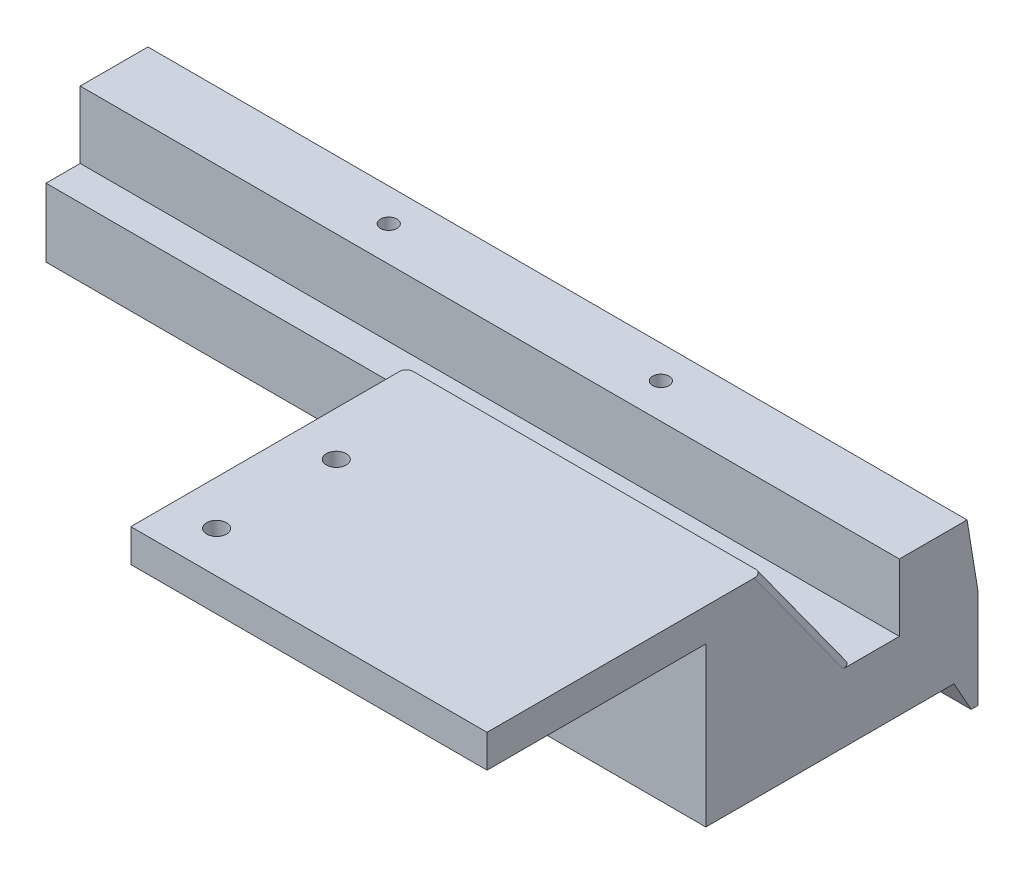
SolidWorks part; units mm, degrees
ref_plane "Płaszczyzna przednia" through (0, 0, 0) normal (0, 0, 1) x (1, 0, 0)
ref_plane "Płaszczyzna górna" through (0, 0, 0) normal (0, 1, 0) x (1, 0, 0)
ref_plane "Płaszczyzna prawa" through (0, 0, 0) normal (1, 0, 0) x (0, 0, -1)
sketch "Szkic1" plane through (0, 0, 0) normal (0, 0, 1) x (1, 0, 0)
  line L1 (-58.3066, 32.0248) -> (61.4934, 32.0248)
  line L2 (-58.3066, 32.0248) -> (-58.3066, 22.0248)
  line L3 (-58.3066, 22.0248) -> (61.4934, 22.0248)
  line L4 (61.4934, 32.0248) -> (61.4934, 22.0248)
  dimension "D1" = 119.8
  dimension "D2" = 10
extrude "Dodanie-wyciągnięcie2" add sketch "Szkic1" along normal blind 38.3 contours L2 L3 L4 L1
sketch "Szkic21" plane through (0, 32.0248, 0) normal (0, 1, 0) x (1, 0, 0)
  line L0 (61.4934, -38.3) -> (61.4934, 0) construction
  line L1 (-58.3066, 0) -> (61.4934, 0)
  line L2 (-58.3066, 0) -> (-58.3066, -10)
  line L3 (-58.3066, -10) -> (61.4934, -10)
  line L4 (61.4934, 0) -> (61.4934, -10)
extrude "Dodanie-wyciągnięcie3" add sketch "Szkic21" along normal blind 9.8
sketch "Szkic22" plane through (0, 22.0248, 0) normal (0, -1, 0) x (1, 0, 0)
  line L0 (-58.3066, 4.88) -> (-18.3066, 4.88) construction
  line L1 (-58.3066, 38.3) -> (-58.3066, 0) construction
  line L2 (-18.3066, 4.88) -> (21.4934, 4.88) construction
  line L3 (21.4934, 4.88) -> (61.4934, 4.88) construction
  line L4 (61.4934, 38.3) -> (61.4934, 0) construction
  line L5 (1.9729, 4.88) -> (1.9729, 0) construction
  line L6 (-58.3066, 0) -> (61.4934, 0) construction
hole_wizard "Pogłębienie walcowe pod M2 wkręt do części metalowych z łbem stożkowym ściętym2" positions "Szkic23" profile "Szkic24" counterbore size "M2" standard "Ansi Metric" end condition through all
sketch "Szkic23" plane through (0, 22.0248, 0) normal (0, -1, 0) x (-1, 0, 0)
  point P0 (-21.4934, -4.88)
  point P3 (18.3066, -4.88)
sketch "Szkic24" plane through (21.4934, 22.0248, 4.88) normal (1, 0, 0) x (0, 0, -1)
  line L0 (0, 0) -> (0, 19.8)
  line L1 (0, 19.8) -> (1.2, 19.8)
  line L3 (1.2, 19.8) -> (1.2, 1.6)
  line L4 (1.2, 1.6) -> (2.5, 1.6)
  line L5 (2.5, 1.6) -> (2.5, 0)
  line L7 (2.5, 0) -> (0, 0)
  line L11 (0, -6.35) -> (0, 107.95) construction
  dimension "Średnica otworu na wylot" = 2.4
  dimension "Głębokość otworu na wylot" = 19.8
  dimension "Średnica pogłębienia walcowego" = 5
  dimension "Głębokość pogłębienia walcowego" = 1.6
sketch "Szkic28" plane through (0, 22.0248, 0) normal (0, -1, 0) x (1, 0, 0)
  line L0 (36.4934, 0) -> (36.4934, 23.3) construction
  line L1 (-58.3066, 0) -> (61.4934, 0) construction
  line L2 (36.4934, 23.3) -> (61.4934, 23.3) construction
  line L3 (61.4934, 38.3) -> (61.4934, 0) construction
  line L4 (-58.3066, 38.3) -> (61.4934, 38.3) construction
  circle A0 centre (36.4934, 23.3) radius 11.1
  dimension "D1" = 15
extrude "Wytnij-wyciągnięcie1" cut sketch "Szkic28" against normal blind 7.2
sketch "Szkic31" plane through (61.4934, 0, 0) normal (1, 0, 0) x (0, 0, -1)
  line L0 (-10, 32.0248) -> (-10, 71.9248)
  line L2 (0, 41.2325) -> (0, 32.0248)
  line L6 (0, 41.8248) -> (0, 22.0248) construction
  line L8 (0, 32.0248) -> (1.5, 32.0248)
  line L10 (-10, 32.0248) -> (1.5, 32.0248)
  line L12 (-10, 71.9248) -> (-5, 71.9248)
  line L13 (-5, 71.9248) -> (1.5, 32.0248)
  line L14 (-0.4105, 43.7521) -> (0.2752, 39.543)
  line L15 (0.2752, 39.543) -> (3.3905, 40.0505)
  line L16 (3.3905, 40.0505) -> (-0.4105, 43.7521)
  line M5 (0, 22.0248) -> (0, 41.8248)
  line M6 (0, 41.8248) -> (-10, 41.8248)
extrude "Wytnij-wyciągnięcie4" cut sketch "Szkic31" against normal blind 124.8 contours L13 M6 M5 region at (61.4934, 41.6274, 0.0322)
extrude "Dodanie-wyciągnięcie5" add sketch "Szkic31<5>" against normal blind 119.8 contours L13 L8 M5 region at (61.4934, 35.0941, -0.5)
sketch "Szkic31<5>" plane through (61.4934, 0, 0) normal (1, 0, 0) x (0, 0, -1) same geometry as "Szkic31"
sketch "Szkic34" plane through (0, 0, 0) normal (0, 0, -1) x (-1, 0, 0)
  line L1 (-61.4934, 32.0248) -> (58.3066, 32.0248)
  line L2 (-61.4934, 32.0248) -> (-61.4934, 22.0248)
  line L3 (-61.4934, 22.0248) -> (58.3066, 22.0248)
  line L4 (58.3066, 32.0248) -> (58.3066, 22.0248)
extrude "Dodanie-wyciągnięcie6" add sketch "Szkic34" along normal blind 1.5
sketch "Szkic37" plane through (0, 32.0248, 0) normal (0, 1, 0) x (1, 0, 0)
  line L1 (61.4934, -38.3) -> (9.3934, -38.3)
  line L2 (61.4934, -38.3) -> (61.4934, -30)
  line L3 (61.4934, -30) -> (9.3934, -30)
  line L4 (9.3934, -38.3) -> (9.3934, -30)
extrude "Dodanie-wyciągnięcie8" add sketch "Szkic37" along normal blind 18
sketch "Szkic38" plane through (0, 0, 38.3) normal (0, 0, 1) x (1, 0, 0)
  line L0 (61.4934, 50.0248) -> (61.4934, 22.0248) construction
  line L1 (9.3934, 50.0248) -> (61.4934, 50.0248)
  line L2 (9.3934, 50.0248) -> (9.3934, 45.2248)
  line L3 (9.3934, 45.2248) -> (61.4934, 45.2248)
  line L4 (61.4934, 50.0248) -> (61.4934, 45.2248)
extrude "Dodanie-wyciągnięcie11" add sketch "Szkic38" along normal blind 32
sketch "Szkic40" plane through (0, 45.2248, 0) normal (0, -1, 0) x (1, 0, 0)
  line L0 (9.3934, 44.15) -> (61.4934, 44.15) construction
  line L1 (9.3934, 70.3) -> (9.3934, 38.3) construction
  line L2 (61.4934, 70.3) -> (61.4934, 38.3) construction
  line L3 (9.3934, 38.3) -> (61.4934, 38.3) construction
  line L4 (49.3934, 44.15) -> (49.3934, 38.3) construction
  line L5 (9.3934, 66.65) -> (61.4934, 66.65) construction
  line L6 (9.3934, 70.3) -> (61.4934, 70.3) construction
  line L7 (9.3934, 55.4) -> (61.4934, 55.4) construction
  line L8 (39.019, 44.15) -> (44.019, 44.15)
  line L9 (39.019, 44.15) -> (39.019, 42.65)
  line L10 (39.019, 42.65) -> (44.019, 42.65)
  line L11 (44.019, 44.15) -> (44.019, 42.65)
  line L12 (32.3245, 66.65) -> (32.3245, 55.4) construction
  line L13 (32.3245, 55.4) -> (32.3245, 44.15) construction
  dimension "D1" = 11.25
  dimension "D2" = 12.1
  dimension "D3" = 3.65
ref_plane "Płaszczyzna1" through (0, 43.2248, 0) normal (0, -1, 0) x (-1, 0, 0)
sketch "Szkic41" plane through (0, 43.2248, 0) normal (0, -1, 0) x (-1, 0, 0)
  line L0 (-39.019, -42.65) -> (-44.019, -42.65) construction
  line L1 (-43.4902, -42.65) -> (-39.5477, -42.65)
  line L2 (-43.4902, -42.65) -> (-43.4902, -44.15)
  line L3 (-43.4902, -44.15) -> (-39.5477, -44.15)
  line L4 (-39.5477, -42.65) -> (-39.5477, -44.15)
  line L5 (-39.019, -44.15) -> (-44.019, -44.15) construction
  line L6 (-44.019, -43.4) -> (-43.4902, -43.4) construction
  line L11 (-44.019, -44.15) -> (-44.019, -42.65) construction
  line L12 (-39.5477, -43.4) -> (-39.019, -43.4) construction
  line L14 (-39.019, -44.15) -> (-39.019, -42.65) construction
loft "Wyciągnięcie po profilach5" add profiles "Szkic40", "Szkic41" connector at (39.019, 45.2248, 42.65) connector at (39.5477, 43.2248, 42.65)
fillet "Zaokrąglenie5" radius 0.5 8 edges
pattern_linear "Szyk liniowy2" count 2 spacing 24.2 along (0, 0, 1) of "Zaokrąglenie5", "Wyciągnięcie po profilach5"
sketch "Szkic43" plane through (0, 45.2248, 0) normal (0, -1, 0) x (1, 0, 0)
  line L0 (9.3934, 64.25) -> (15.8934, 64.25) construction
  line L1 (9.3934, 70.3) -> (9.3934, 38.3) construction
  line L3 (9.3934, 46.75) -> (15.8934, 46.75) construction
  line L4 (15.8934, 70.3) -> (15.8934, 64.25) construction
  line L7 (9.3934, 70.3) -> (61.4934, 70.3) construction
  line L8 (15.8934, 64.25) -> (15.8934, 46.75) construction
  line L9 (15.8934, 46.75) -> (15.8934, 38.3) construction
  line L10 (9.3934, 38.3) -> (61.4934, 38.3) construction
  line L11 (15.8934, 64.25) -> (61.4934, 64.25) construction
  line L12 (61.4934, 70.3) -> (61.4934, 38.3) construction
  line L13 (15.8934, 46.75) -> (61.4934, 46.75) construction
  line L14 (43.5018, 44.15) -> (39.5361, 44.15) construction
  line L15 (41.519, 44.15) -> (41.519, 46.75)
  line L16 (41.519, 46.75) -> (41.519, 64.25)
  line L17 (41.519, 64.25) -> (41.519, 66.85)
  line L18 (39.5361, 66.85) -> (43.5018, 66.85) construction
  dimension "D1" = 8.45
  dimension "D2" = 45.6
  dimension "18.1" = 17.5
hole_wizard "Otwór pod śrubę M2.51" positions "Szkic44" profile "Szkic45" hole size "M2.5" standard "ISO" end condition through all
sketch "Szkic44" plane through (0, 45.2248, 0) normal (0, -1, 0) x (-1, 0, 0)
  point P0 (-15.8934, -46.75)
  point P3 (-15.8934, -64.25)
sketch "Szkic45" plane through (15.8934, 45.2248, 46.75) normal (1, 0, 0) x (0, 0, -1)
  line L0 (0, 0) -> (0, 4.8)
  line L1 (0, 4.8) -> (1.45, 4.8)
  line L2 (1.45, 4.8) -> (1.45, 0)
  line L5 (1.45, 0) -> (0, 0)
  line L11 (0, -6.35) -> (0, 107.95) construction
  dimension "Średnica otworu na wylot" = 2.9
  dimension "Głębokość otworu na wylot" = 4.8
sketch "Szkic52" plane through (61.4934, 0, 0) normal (1, 0, 0) x (0, 0, -1)
  line L0 (-30, 50.0248) -> (-17, 32.0248)
  line L1 (-30, 32.0248) -> (-10, 32.0248) construction
  line L2 (-30, 50.0248) -> (-30, 32.0248) construction
  dimension "D1" = 13
rib "Żebro7" sketch "Szkic52" sketch "Szkic52" thickness 3 extrusion direction parallel to sketch draft on no parameters "D1"=3
fillet "Zaokrąglenie7" radius 1 2 edges at (61.4934, 41.0248, 23.5) (58.4934, 41.0248, 23.5)
pattern_linear "Szyk liniowy6" count 5 spacing 12.25 along (-1, 0, 0) of "Żebro7", "Zaokrąglenie7"
fillet "Zaokrąglenie8" radius 1 1 edges at (9.3934, 41.0248, 30)
sketch "Szkic53" plane through (0, 0, 38.3) normal (0, 0, 1) x (1, 0, 0)
  line L1 (9.3934, 32.0248) -> (-58.3066, 32.0248)
  line L2 (9.3934, 32.0248) -> (9.3934, 22.0248)
  line L3 (9.3934, 22.0248) -> (-58.3066, 22.0248)
  line L4 (-58.3066, 32.0248) -> (-58.3066, 22.0248)
extrude "Wytnij-wyciągnięcie5" cut sketch "Szkic53" against normal blind 23.3
sketch "Szkic54" plane through (61.4934, 0, 0) normal (1, 0, 0) x (0, 0, -1)
  line L0 (-2, 22.0248) -> (1.5, 22.0248)
  line L1 (1.5, 17.5248) -> (0.5, 17.5248)
  line L2 (-4.88, 22.0248) -> (0, 22.0248) construction
  line L3 (-38.3, 22.0248) -> (1.5, 22.0248) construction
  line L4 (1.5, 22.0248) -> (1.5, 17.5248)
  line L6 (0.5, 17.5248) -> (-2, 22.0248)
extrude "Dodanie-wyciągnięcie12" add sketch "Szkic54" against normal blind 119.8
sketch "Szkic55" plane through (0, 22.0248, 0) normal (0, -1, 0) x (1, 0, 0)
  line L0 (-58.3066, 8.5) -> (-33.3066, 8.5) construction
  line L1 (-58.3066, 15) -> (-58.3066, 2) construction
  line L2 (-33.3066, 8.5) -> (-8.3066, 8.5) construction
  circle A0 centre (-45.8066, 8.5) radius 5.1
  circle A1 centre (-8.3066, 8.5) radius 5.1
extrude "Wytnij-wyciągnięcie6" cut sketch "Szkic55" against normal blind 4.1
